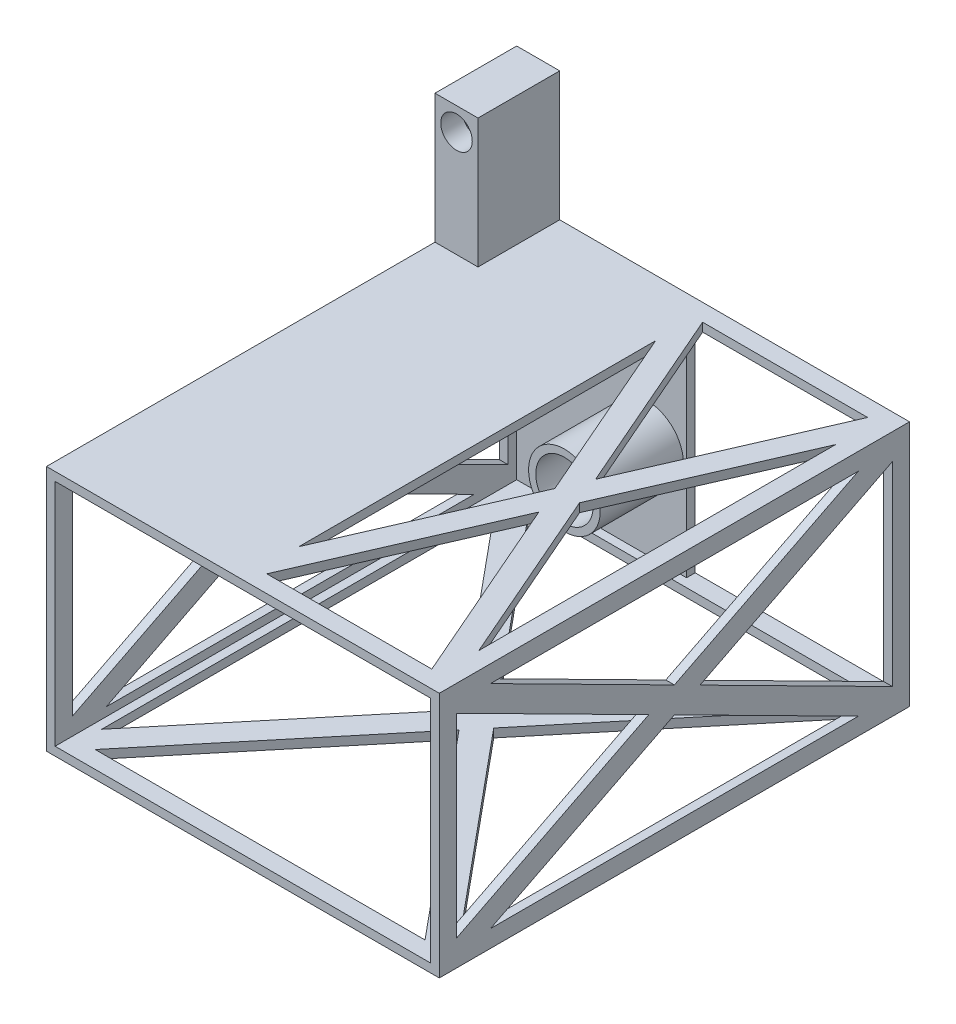
SolidWorks part; units mm, degrees
ref_plane "Front Plane" through (0, 0, 0) normal (0, 0, 1) x (1, 0, 0)
ref_plane "Top Plane" through (0, 0, 0) normal (0, 1, 0) x (1, 0, 0)
ref_plane "Right Plane" through (0, 0, 0) normal (1, 0, 0) x (0, 0, -1)
sketch "Sketch1" plane through (0, 0, 0) normal (0, 0, 1) x (1, 0, 0)
  line L1 (0, 0) -> (137, 0)
  line L2 (0, 0) -> (0, -86)
  line L3 (0, -86) -> (137, -86)
  line L4 (137, 0) -> (137, -86)
  line L5 (3, -3) -> (134, -3)
  line L6 (3, -3) -> (3, -83)
  line L7 (3, -83) -> (134, -83)
  line L8 (134, -3) -> (134, -83)
  dimension "D1" = 86
  dimension "D2" = 137
  dimension "D3" = 3
  dimension "D4" = 3
  dimension "D5" = 3
  dimension "D6" = 3
extrude "Boss-Extrude1" add sketch "Sketch1" along normal blind 164
sketch "Sketch2" plane through (0, -86, 0) normal (0, -1, 0) x (1, 0, 0)
  line L0 (0, 164) -> (0, 0) construction
  line L1 (6, 158) -> (131, 158)
  line L2 (6, 158) -> (6, 6)
  line L3 (6, 6) -> (131, 6)
  line L4 (131, 158) -> (131, 6)
  line L5 (0, 164) -> (137, 164) construction
  line L6 (137, 164) -> (137, 0) construction
  line L7 (0, 0) -> (137, 0) construction
  line L8 (0, 158) -> (131, 0)
  line L9 (131, 0) -> (137, 6)
  line L12 (131, 164) -> (0, 6)
  line L13 (0, 6) -> (6, 0)
  line L14 (6, 0) -> (137, 158)
  line L15 (137, 158) -> (131, 164)
  line L16 (137, 6) -> (6, 164)
  line L17 (6, 164) -> (0, 158)
  point P12 (6, 164)
  point P13 (0, 158)
  point P14 (0, 6)
  point P15 (6, 0)
  point P16 (137, 6)
  point P17 (131, 0)
  point P18 (137, 158)
  point P19 (131, 164)
  dimension "D1" = 6
  dimension "D2" = 6
  dimension "D3" = 6
  dimension "D4" = 6
  dimension "D5" = 6
  dimension "D6" = 6
  dimension "D7" = 6
  dimension "D8" = 6
  dimension "D9" = 6
  dimension "D10" = 6
  dimension "D11" = 6
  dimension "D12" = 6
extrude "Cut-Extrude1" cut sketch "Sketch2" against normal blind 3 contours L1 L4 L3 L2
extrude "Boss-Extrude2" add sketch "Sketch2<3>" against normal blind 3 contours L8 L9 L16 L17
sketch "Sketch2<3>" plane through (0, -86, 0) normal (0, -1, 0) x (1, 0, 0) same geometry as "Sketch2"
extrude "Boss-Extrude3" add sketch "Sketch2<4>" against normal blind 3 contours L12 L13 L14 L15
sketch "Sketch2<4>" plane through (0, -86, 0) normal (0, -1, 0) x (1, 0, 0) same geometry as "Sketch2"
sketch "Sketch3" plane through (137, 0, 0) normal (1, 0, 0) x (0, 0, -1)
  line L0 (-158, -86) -> (0, -86) construction
  line L1 (-158, -80) -> (-6, -80)
  line L2 (-158, -80) -> (-158, -6)
  line L3 (-158, -6) -> (-6, -6)
  line L4 (-6, -80) -> (-6, -6)
  line L5 (-164, -86) -> (-164, 0) construction
  line L6 (-164, 0) -> (0, 0) construction
  line L7 (0, -86) -> (0, 0) construction
  line L8 (-158, -86) -> (0, -6)
  line L9 (0, -6) -> (-6, 0)
  line L12 (-164, -6) -> (-6, -86)
  line L13 (-6, -86) -> (0, -80)
  line L14 (0, -80) -> (-158, 0)
  line L15 (-158, 0) -> (-164, -6)
  line L16 (-6, 0) -> (-164, -80)
  line L17 (-164, -80) -> (-158, -86)
  point P12 (-164, -80)
  point P13 (-164, -6)
  point P14 (-158, 0)
  point P15 (-6, 0)
  point P16 (0, -6)
  point P17 (0, -80)
  dimension "D1" = 6
  dimension "D2" = 6
  dimension "D3" = 6
  dimension "D4" = 6
  dimension "D5" = 6
  dimension "D6" = 6
  dimension "D7" = 6
  dimension "D8" = 6
  dimension "D9" = 6
  dimension "D10" = 6
extrude "Cut-Extrude2" cut sketch "Sketch3" against normal blind 3 contours L2 L3 L4 L1
extrude "Boss-Extrude4" add sketch "Sketch3<3>" against normal blind 3 contours L12 L13 L14 L15
sketch "Sketch3<3>" plane through (137, 0, 0) normal (1, 0, 0) x (0, 0, -1) same geometry as "Sketch3"
extrude "Boss-Extrude5" add sketch "Sketch3<5>" against normal blind 3 contours L8 L9 L16 L17
sketch "Sketch3<5>" plane through (137, 0, 0) normal (1, 0, 0) x (0, 0, -1) same geometry as "Sketch3"
sketch "Sketch4" plane through (0, 0, 0) normal (-1, 0, 0) x (0, 0, 1)
  line L0 (6, 0) -> (164, -80)
  line L1 (6, -6) -> (158, -6)
  line L2 (6, -6) -> (6, -80)
  line L3 (6, -80) -> (158, -80)
  line L4 (158, -6) -> (158, -80)
  line L5 (164, -80) -> (158, -86)
  line L6 (158, -86) -> (0, -6)
  line L7 (0, -6) -> (6, 0)
  line L8 (158, 0) -> (0, -80)
  line L9 (0, -80) -> (6, -86)
  line L10 (6, -86) -> (164, -6)
  line L11 (164, -6) -> (158, 0)
extrude "Cut-Extrude3" cut sketch "Sketch4" against normal blind 3 contours L4 L3 L2 L1
extrude "Boss-Extrude6" add sketch "Sketch4<4>" against normal blind 3 contours L10 L11 L8 L9
sketch "Sketch4<4>" plane through (0, 0, 0) normal (-1, 0, 0) x (0, 0, 1) same geometry as "Sketch4"
extrude "Boss-Extrude7" add sketch "Sketch4<5>" against normal blind 3 contours L0 L5 L6 L7
sketch "Sketch4<5>" plane through (0, 0, 0) normal (-1, 0, 0) x (0, 0, 1) same geometry as "Sketch4"
sketch "Sketch6" plane through (0, 0, 0) normal (0, 0, -1) x (-1, 0, 0)
  line L0 (0, -86) -> (-137, -86) construction
  line L1 (0, 0) -> (-62.23, 0)
  line L2 (0, 0) -> (0, -86)
  line L3 (0, -86) -> (-62.23, -86)
  line L4 (-62.23, 0) -> (-62.23, -86)
  dimension "D1" = 62.23
extrude "Boss-Extrude8" add sketch "Sketch6" against normal blind 3
sketch "Sketch7" plane through (0, 0, 0) normal (0, 1, 0) x (1, 0, 0)
  line L0 (137, -164) -> (0, -164) construction
  line L1 (0, 0) -> (62.23, 0)
  line L2 (0, 0) -> (0, -164)
  line L3 (0, -164) -> (62.23, -164)
  line L4 (62.23, 0) -> (62.23, -164)
  line L5 (137, 0) -> (0, 0) construction
  line L6 (68.23, -6) -> (131, -6)
  line L7 (68.23, -6) -> (68.23, -158)
  line L8 (68.23, -158) -> (131, -158)
  line L9 (131, -6) -> (131, -158)
  line L10 (137, -164) -> (137, 0) construction
  line L11 (68.23, 0) -> (137, -158)
  line L12 (137, -158) -> (131, -164)
  line L13 (131, -164) -> (62.23, -6)
  line L14 (62.23, -6) -> (68.23, 0)
  line L15 (131, 0) -> (62.23, -158)
  line L16 (62.23, -158) -> (68.23, -164)
  line L17 (68.23, -164) -> (137, -6)
  line L18 (137, -6) -> (131, 0)
  point P15 (68.23, 0)
  point P16 (62.23, -6)
  point P17 (68.23, -164)
  point P18 (62.23, -158)
  point P19 (131, -164)
  point P20 (137, -158)
  point P21 (137, -6)
  point P22 (131, 0)
  dimension "D1" = 62.23
  dimension "D2" = 6
  dimension "D3" = 6
  dimension "D4" = 6
  dimension "D5" = 6
  dimension "D6" = 6
  dimension "D7" = 6
  dimension "D8" = 6
  dimension "D9" = 6
  dimension "D10" = 6
  dimension "D11" = 6
  dimension "D12" = 6
extrude "Cut-Extrude4" cut sketch "Sketch7" against normal blind 3 contours L6 L9 L8 L7
extrude "Boss-Extrude9" add sketch "Sketch7<3>" against normal blind 3 contours L11 L12 L13 L14
sketch "Sketch7<3>" plane through (0, 0, 0) normal (0, 1, 0) x (1, 0, 0) same geometry as "Sketch7"
extrude "Boss-Extrude10" add sketch "Sketch7<4>" against normal blind 3 contours L15 L16 L17 L18
sketch "Sketch7<4>" plane through (0, 0, 0) normal (0, 1, 0) x (1, 0, 0) same geometry as "Sketch7"
sketch "Sketch8" plane through (0, 0, 0) normal (0, 0, -1) x (-1, 0, 0)
  line L0 (0, 0) -> (0, -86) construction
  line L1 (-137, 0) -> (0, 0) construction
  circle A0 centre (-48.64, -48.9) radius 10
  circle A1 centre (-48.64, -48.9) radius 12.5
  dimension "D1" = 20
  dimension "D4" = 25
  dimension "D2" = 48.64
  dimension "D3" = 48.9
extrude "Boss-Extrude11" add sketch "Sketch8" against normal blind 32
extrude "Cut-Extrude8" cut sketch "Sketch8<4>" against normal blind 32 contours A0
sketch "Sketch8<4>" plane through (0, 0, 0) normal (0, 0, -1) x (-1, 0, 0) same geometry as "Sketch8"
sketch "Sketch9" plane through (0, 0, 0) normal (-1, 0, 0) x (0, 0, 1)
  line L0 (0, -38.9) -> (0, -58.9) construction
  line L1 (6, -41.4) -> (0, -41.4)
  line L2 (6, -41.4) -> (6, -56.4)
  line L3 (6, -56.4) -> (0, -56.4)
  line L4 (0, -41.4) -> (0, -56.4)
  line L5 (0, 0) -> (0, -86) construction
  line L6 (58, -41.4) -> (52, -41.4)
  line L7 (58, -41.4) -> (58, -56.4)
  line L8 (58, -56.4) -> (52, -56.4)
  line L9 (52, -41.4) -> (52, -56.4)
  line L11 (58, -28.3795) -> (52, -28.3795)
  line L12 (58, -28.3795) -> (58, -57.0445)
  line L13 (58, -57.0445) -> (52, -57.0445)
  line L14 (52, -28.3795) -> (52, -57.0445)
  dimension "D1" = 7.5
  dimension "D2" = 15
  dimension "D3" = 6
  dimension "D4" = 6
  dimension "D5" = 52
  dimension "D6" = 15
  dimension "D7" = 0
extrude "Boss-Extrude12" add sketch "Sketch9" along normal blind 15 contours L7 L8 L9 L6
extrude "Boss-Extrude13" add sketch "Sketch9<3>" along normal blind 12 contours L6 L9 L8 L7
sketch "Sketch9<3>" plane through (0, 0, 0) normal (-1, 0, 0) x (0, 0, 1) same geometry as "Sketch9"
extrude "Boss-Extrude14" add sketch "Sketch9<4>" along normal blind 15 contours L1 L4 L3 L2
sketch "Sketch9<4>" plane through (0, 0, 0) normal (-1, 0, 0) x (0, 0, 1) same geometry as "Sketch9"
fillet "Fillet1" radius 3 4 edges at (-15, -41.4, 3) (-15, -56.4, 3) (-15, -41.4, 55) (-15, -56.4, 55)
sketch "Sketch11" plane through (0, 0, 0) normal (0, 1, 0) x (1, 0, 0)
  line L16 (0, 0) -> (15, 0)
  line L17 (0, 0) -> (0, -10)
  line L18 (0, -10) -> (15, -10)
  line L19 (15, 0) -> (15, -10)
  dimension "D1" = 15
  dimension "D2" = 10
extrude "Boss-Extrude17" add sketch "Sketch9<5>" against normal blind 3 contours L14 L13 L12 L11
sketch "Sketch9<5>" plane through (0, 0, 0) normal (-1, 0, 0) x (0, 0, 1) same geometry as "Sketch9"
sketch "Sketch16" plane through (0, 0, 58) normal (0, 0, 1) x (1, 0, 0)
  line L0 (-15, -48.9) -> (0, -48.9) construction
  line L2 (-15, -44.4) -> (-15, -53.4) construction
  line L3 (0, 0) -> (0, -86) construction
  circle A0 centre (-7.5, -48.9) radius 2
  point P3 (-15, -48.9)
  dimension "D1" = 4
extrude "Cut-Extrude13" cut sketch "Sketch16" against normal blind 64
extrude "Boss-Extrude18" add sketch "Sketch11" along normal blind 45 contours L19 L18 L17 L16
sketch "Sketch18" plane through (0, 0, 10) normal (0, 0, 1) x (1, 0, 0)
  line L0 (15, 45) -> (15, 0) construction
  line L1 (0, 0) -> (15, 0) construction
  circle A0 centre (7.5, 37) radius 1
  dimension "D1" = 2
  dimension "D2" = 7.5
  dimension "D3" = 37
extrude "Cut-Extrude14" cut sketch "Sketch18" against normal blind 10 contours A0
sketch "Sketch19" plane through (0, 0, 10) normal (0, 0, 1) x (1, 0, 0)
  line L0 (0, 0) -> (15, 0) construction
  line L1 (0, 45) -> (15, 45)
  line L2 (0, 45) -> (0, 0)
  line L3 (0, 0) -> (15, 0)
  line L4 (15, 45) -> (15, 0)
  line L5 (137, 0) -> (0, 0) construction
  dimension "D1" = 15
extrude "Boss-Extrude19" add sketch "Sketch19" along normal blind 2
sketch "Sketch20" plane through (0, 0, 12) normal (0, 0, 1) x (1, 0, 0)
  circle A0 centre (7.5, 37) radius 1.65
  dimension "D1" = 3.3
extrude "Cut-Extrude15" cut sketch "Sketch20" against normal blind 2 contours A0
sketch "Sketch21" plane through (0, 0, 12) normal (0, 0, 1) x (1, 0, 0)
  line L0 (0, 0) -> (15, 0) construction
  line L1 (0, 45) -> (15, 45)
  line L2 (0, 45) -> (0, 0)
  line L3 (0, 0) -> (15, 0)
  line L4 (15, 45) -> (15, 0)
  circle A0 centre (7.5, 37) radius 3.25
  dimension "D1" = 6.5
  dimension "D2" = 15
extrude "Boss-Extrude20" add sketch "Sketch21" along normal blind 9 contours L4 L3 L2 L1
extrude "Cut-Extrude16" cut sketch "Sketch21<3>" along normal blind 9 contours A0
sketch "Sketch21<3>" plane through (0, 0, 12) normal (0, 0, 1) x (1, 0, 0) same geometry as "Sketch21"
sketch "Sketch25" plane through (0, 0, 21) normal (0, 0, 1) x (1, 0, 0)
  line L1 (0, 45) -> (15, 45)
  line L2 (0, 45) -> (0, 0)
  line L3 (0, 0) -> (15, 0)
  line L4 (15, 45) -> (15, 0)
  circle A0 centre (7.5, 37) radius 5.5
  dimension "D1" = 11
extrude "Boss-Extrude21" add sketch "Sketch25" along normal blind 7.5
sketch "Sketch26" plane through (0, 0, 0) normal (0, 1, 0) x (1, 0, 0)
  line L1 (0, -52) -> (15, -52)
  line L2 (0, -52) -> (0, -58)
  line L3 (0, -58) -> (15, -58)
  line L4 (15, -52) -> (15, -58)
  dimension "D1" = 15
  dimension "D2" = 6
